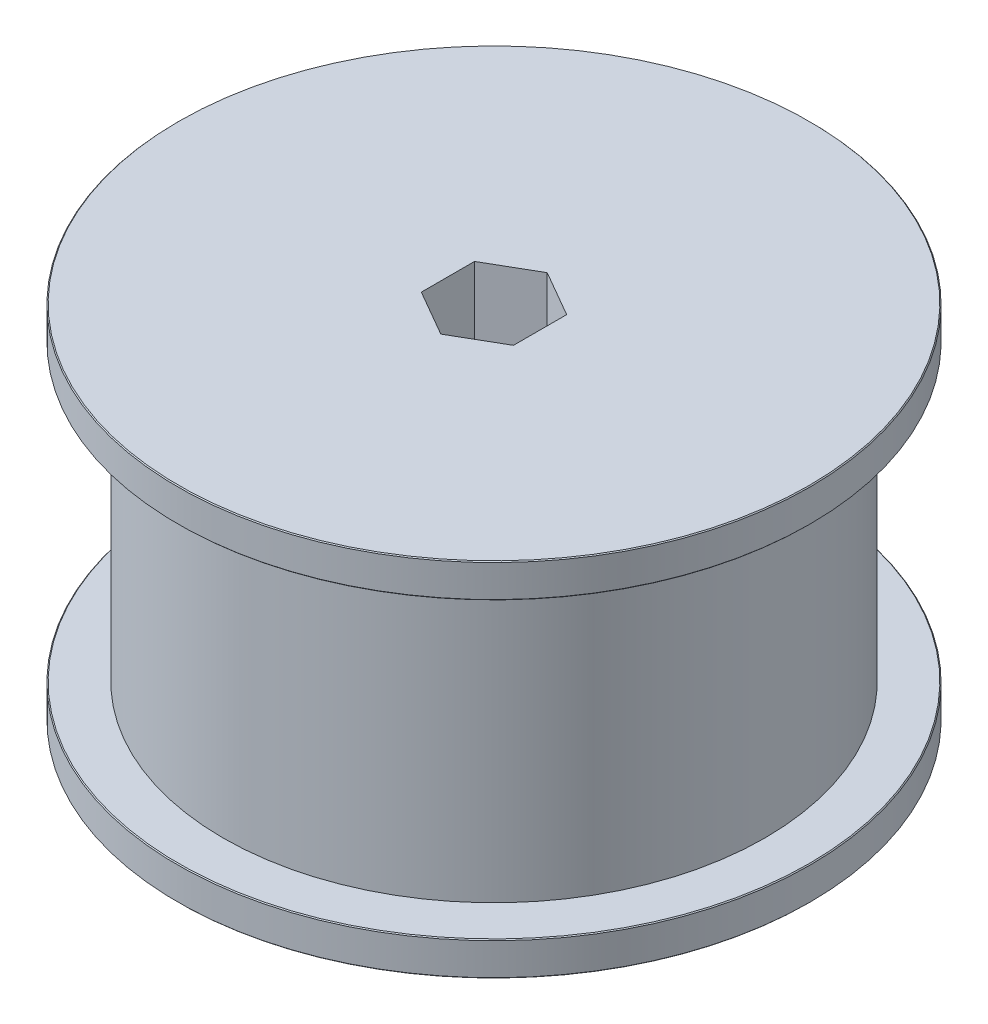
SolidWorks part; units mm, degrees
material "6061-T6 (SS)"
ref_plane "Front Plane" through (0, 0, 0) normal (0, 0, 1) x (1, 0, 0)
ref_plane "Top Plane" through (0, 0, 0) normal (0, 1, 0) x (1, 0, 0)
ref_plane "Right Plane" through (0, 0, 0) normal (1, 0, 0) x (0, 0, -1)
sketch "Sketch1" plane through (0, 0, 0) normal (0, 0, 1) x (1, 0, 0)
  line L0 (0, 0) -> (44.45, 0)
  line L1 (44.45, 0) -> (44.45, 4.7625)
  line L2 (44.45, 4.7625) -> (38.1, 4.7625)
  line L3 (38.1, 4.7625) -> (38.1, 46.0375)
  line L4 (38.1, 46.0375) -> (44.45, 46.0375)
  line L5 (44.45, 46.0375) -> (44.45, 50.8)
  line L6 (44.45, 50.8) -> (0, 50.8)
  line L7 (0, 50.8) -> (0, 0) construction
  line L8 (0, 0) -> (0, 4.7752)
  line L10 (0, 4.7752) -> (0, 46.0248)
  line L12 (0, 46.0248) -> (0, 50.8)
  dimension "D1" = 76.2
  dimension "D2" = 88.9
  dimension "D3" = 41.275
  dimension "D4" = 50.8
revolve "Revolve1" add sketch "Sketch1" angle 360 about L7
chamfer "Chamfer1" distance 0.127 angle 45 4 edges at (-44.45, 46.0375, 0) (-44.45, 4.7625, 0) (-44.45, 0, 0) (-44.45, 50.8, 0)
sketch "Sketch2" plane through (0, 0, 0) normal (0, -1, 0) x (1, 0, 0)
  line L1 (0, 7.479) -> (-6.477, 3.7395)
  line L2 (-6.477, 3.7395) -> (-6.477, -3.7395)
  line L3 (-6.477, -3.7395) -> (0, -7.479)
  line L4 (0, -7.479) -> (6.477, -3.7395)
  line L5 (6.477, -3.7395) -> (6.477, 3.7395)
  line L6 (6.477, 3.7395) -> (0, 7.479)
  circle A0 centre (0, 0) radius 6.477 construction
  dimension "D1" = 12.954
extrude "Cut-Extrude1" cut sketch "Sketch2" against normal through all both and the other way through all
